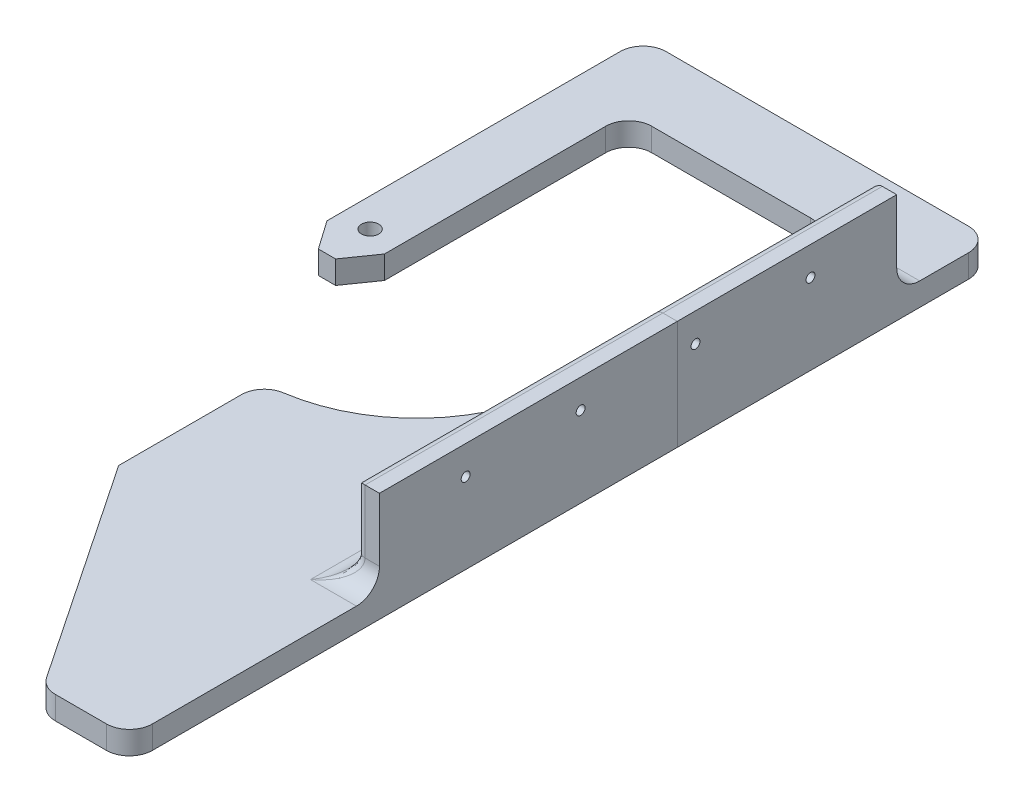
SolidWorks part; units mm, degrees
ref_plane "Front Plane" through (0, 0, 0) normal (0, 0, 1) x (1, 0, 0)
ref_plane "Top Plane" through (0, 0, 0) normal (0, 1, 0) x (1, 0, 0)
ref_plane "Right Plane" through (0, 0, 0) normal (1, 0, 0) x (0, 0, -1)
sketch "Sketch1" plane through (0, 0, 0) normal (0, 1, 0) x (1, 0, 0)
  line L0 (0, -55) -> (0, 55) construction
  line L1 (0, 37.4806) -> (121.25, 37.4806)
  line L2 (121.25, 37.4806) -> (121.25, -262.5194)
  line L3 (121.25, -262.5194) -> (91.25, -262.5194)
  line L4 (91.25, -262.5194) -> (37.5, -182.5194)
  line L5 (37.5, -182.5194) -> (37.5, -132.5194)
  line L6 (0, 37.4806) -> (0, -82.5194)
  line L7 (0, -82.5194) -> (20, -82.5194)
  line L8 (20, -82.5194) -> (20, 12.4806)
  line L9 (20, 12.4806) -> (91.25, 12.4806)
  line L10 (91.25, 12.4806) -> (91.25, -77.5336)
  arc A0 (91.25, -77.5336) -> (37.5, -132.5194) centre (36.25, -77.5336) cw
  circle A1 centre (10, -67.5194) radius 3
  dimension "D10" = 55
  dimension "D12" = 6
  dimension "D1" = 300
  dimension "D2" = 121.25
  dimension "D3" = 20
  dimension "D4" = 30
  dimension "D5" = 50
  dimension "D6" = 120
  dimension "D7" = 80
  dimension "D8" = 30
  dimension "D9" = 83.75
  dimension "D11" = 25
  dimension "D13" = 15
extrude "Boss-Extrude1" add sketch "Sketch1" along normal blind 8
fillet "Fillet1" radius 8 7 edges at (121.25, 4, 262.5194) (91.25, 4, 262.5194) (0, 4, -37.4806) (91.25, 4, -12.4806) (20, 4, -12.4806) (37.5, 4, 132.5194) (121.25, 4, -37.4806)
sketch "Sketch2" plane through (0, 8, 0) normal (0, 1, 0) x (1, 0, 0)
  line L0 (113.25, 4.4806) -> (121.25, 4.4806)
  line L2 (121.25, 4.4806) -> (121.25, -175.5194)
  line L3 (121.25, -175.5194) -> (113.25, -175.5194)
  line L4 (113.25, -175.5194) -> (113.25, 4.4806)
  line L5 (121.25, -254.5194) -> (121.25, 29.4806) construction
  dimension "D1" = 180
  dimension "D2" = 8
  dimension "D3" = 25
extrude "Boss-Extrude2" add sketch "Sketch2" along normal blind 30
sketch "Sketch3" plane through (113.25, 0, 0) normal (-1, 0, 0) x (0, 0, 1)
  line L1 (-4.4806, 8) -> (175.5194, 8) construction
  line L2 (-4.4806, 38) -> (-4.4806, 8) construction
  circle A0 centre (25.5194, 28) radius 1.55
  circle A1 centre (65.5194, 28) radius 1.55
  circle A2 centre (105.5194, 28) radius 1.55
  circle A3 centre (145.5194, 28) radius 1.55
  dimension "D1" = 3.1
  dimension "D2" = 40
  dimension "D3" = 40
  dimension "D4" = 40
  dimension "D5" = 30
  dimension "D6" = 20
extrude "Cut-Extrude1" cut sketch "Sketch3" against normal through all
fillet "Fillet2" radius 8 3 edges at (117.25, 8, 175.5194) (113.25, 8, 85.5194) (117.25, 8, -4.4806)
fillet "Fillet3" radius 3 5 edges at (110.9069, 10.3431, 177.8625) (110.9069, 10.3431, -6.8238) (113.25, 27, 175.5194) (113.25, 38, 85.5194) (113.25, 27, -4.4806)
chamfer "Chamfer1" distance 10 angle 35 2 edges at (20, 4, 82.5194) (0, 4, 82.5194)
sketch "Sketch4" plane through (0, 38, 0) normal (0, 1, 0) x (1, 0, 0)
  line L0 (106.25, -71.8693) -> (121.25, -71.8693)
  line L3 (106.25, -71.8693) -> (106.25, -82.0216)
  line L4 (106.25, -82.0216) -> (91.0666, -82.0216)
  line L5 (121.25, -175.5194) -> (121.25, 4.4806) construction
  arc A0 (44.3254, -131.9375) -> (91.25, -77.5336) centre (36.25, -77.5336) ccw construction
split "Split1" trim tools "Sketch4" bodies to split 108 resulting bodies 109 110
